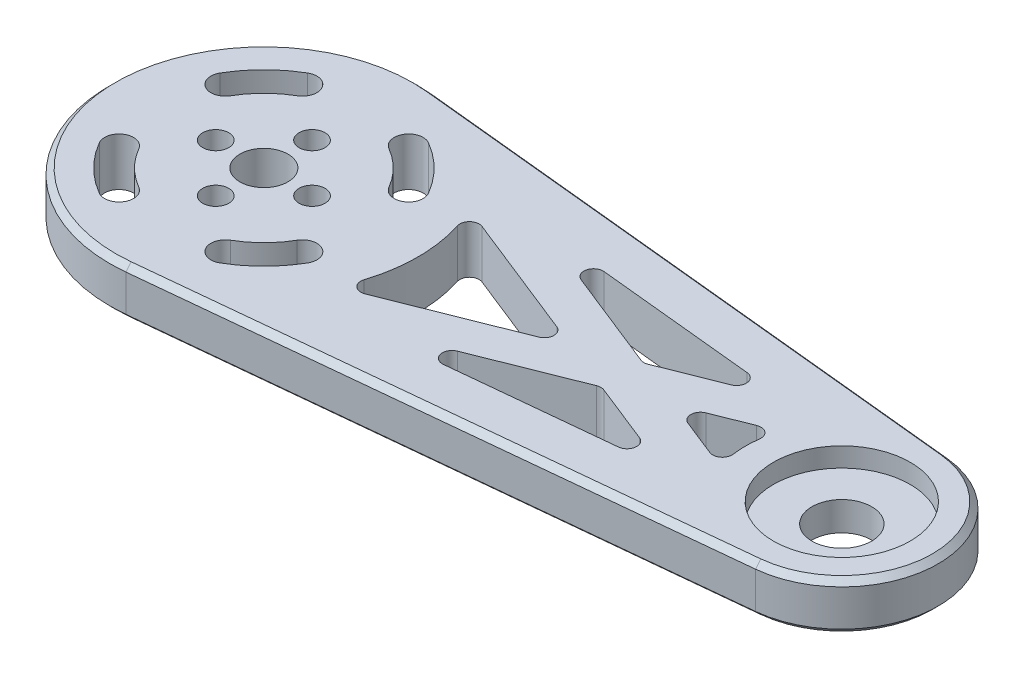
SolidWorks part; units mm, degrees
material "三聚氰胺甲醛树脂"
ref_plane "前视基准面" through (0, 0, 0) normal (0, 0, 1) x (1, 0, 0)
ref_plane "上视基准面" through (0, 0, 0) normal (0, 1, 0) x (1, 0, 0)
ref_plane "右视基准面" through (0, 0, 0) normal (1, 0, 0) x (0, 0, -1)
sketch "草图1" plane through (0, 0, 0) normal (0, 1, 0) x (1, 0, 0)
  line L0 (0, 0) -> (-5.9584, 0) construction
  line L1 (1.6, -15.9198) -> (61, -9.9499)
  line L2 (1.6, 15.9198) -> (61, 9.9499)
  line L3 (19.8889, 9.0565) -> (47.5675, 6.2747)
  line L4 (19.8889, -9.0565) -> (47.5675, -6.2747)
  line L5 (12.6607, 9.783) -> (51.8832, -5.841) construction
  line L6 (12.6607, -9.783) -> (51.8832, 5.841) construction
  line L7 (14.4221, 6.9285) -> (31.8155, 0)
  line L8 (19.8889, 9.0565) -> (37.22, 2.1528)
  line L9 (14.4221, -6.9285) -> (31.8155, 0)
  line L10 (19.8889, -9.0565) -> (37.22, -2.1528)
  line L11 (37.22, 2.1528) -> (47.5675, 6.2747)
  line L12 (42.6245, 0) -> (50.5056, -3.1394)
  line L13 (42.6245, 0) -> (50.5056, 3.1394)
  line L14 (37.22, -2.1528) -> (47.5675, -6.2747)
  line L15 (7.7782, -7.7782) -> (0, 0) construction
  circle A0 centre (0, 0) radius 5 construction
  circle A1 centre (-5, 0) radius 1.35
  circle A2 centre (0, 5) radius 1.35
  circle A3 centre (5, 0) radius 1.35
  circle A4 centre (0, -5) radius 1.35
  arc A5 (1.6, 15.9198) -> (1.6, -15.9198) centre (0, 0) ccw
  circle A6 centre (0, 0) radius 2.5
  arc A7 (50.5056, 3.1394) -> (50.5056, -3.1394) centre (60, 0) ccw
  circle A8 centre (60, 0) radius 3.1
  circle A9 centre (60, 0) radius 7.1
  arc A10 (14.4221, -6.9285) -> (14.4221, 6.9285) centre (0, 0) ccw
  circle A11 centre (0, 0) radius 16 construction
  arc A12 (61, -9.9499) -> (61, 9.9499) centre (60, 0) ccw
  circle A13 centre (60, 0) radius 10 construction
  arc A14 (5.5166, -9.5166) -> (9.5166, -5.5166) centre (0, 0) ccw construction
  arc A15 (6.2689, -10.8144) -> (10.8144, -6.2689) centre (0, 0) ccw
  arc A16 (4.7644, -8.2189) -> (8.2189, -4.7644) centre (0, 0) ccw
  arc A17 (4.7644, -8.2189) -> (6.2689, -10.8144) centre (5.5166, -9.5166) ccw
  arc A18 (10.8144, -6.2689) -> (8.2189, -4.7644) centre (9.5166, -5.5166) ccw
  arc A19 (-9.5166, -5.5166) -> (-5.5166, -9.5166) centre (0, 0) ccw construction
  arc A20 (-10.8144, -6.2689) -> (-6.2689, -10.8144) centre (0, 0) ccw
  arc A21 (-8.2189, -4.7644) -> (-4.7644, -8.2189) centre (0, 0) ccw
  arc A22 (-8.2189, -4.7644) -> (-10.8144, -6.2689) centre (-9.5166, -5.5166) ccw
  arc A23 (-6.2689, -10.8144) -> (-4.7644, -8.2189) centre (-5.5166, -9.5166) ccw
  arc A24 (-5.5166, 9.5166) -> (-9.5166, 5.5166) centre (0, 0) ccw construction
  arc A25 (-6.2689, 10.8144) -> (-10.8144, 6.2689) centre (0, 0) ccw
  arc A26 (-4.7644, 8.2189) -> (-8.2189, 4.7644) centre (0, 0) ccw
  arc A27 (-4.7644, 8.2189) -> (-6.2689, 10.8144) centre (-5.5166, 9.5166) ccw
  arc A28 (-10.8144, 6.2689) -> (-8.2189, 4.7644) centre (-9.5166, 5.5166) ccw
  arc A29 (9.5166, 5.5166) -> (5.5166, 9.5166) centre (0, 0) ccw construction
  arc A30 (10.8144, 6.2689) -> (6.2689, 10.8144) centre (0, 0) ccw
  arc A31 (8.2189, 4.7644) -> (4.7644, 8.2189) centre (0, 0) ccw
  arc A32 (8.2189, 4.7644) -> (10.8144, 6.2689) centre (9.5166, 5.5166) ccw
  arc A33 (6.2689, 10.8144) -> (4.7644, 8.2189) centre (5.5166, 9.5166) ccw
  point P15 (0, 0)
  point P36 (7.7782, -7.7782)
  point P53 (-7.7782, -7.7782)
  point P60 (-7.7782, 7.7782)
  point P67 (7.7782, 7.7782)
  point P72 (0, 0)
  dimension "D1" = 10
  dimension "D2" = 2.7
  dimension "D4" = 20
  dimension "D5" = 32
  dimension "D6" = 5
  dimension "D7" = 6.2
  dimension "D8" = 14.2
  dimension "D15" = 11
  dimension "D16" = 1.5
  dimension "D3" = 60
  dimension "D9" = 5
  dimension "D10" = 5
  dimension "D11" = 2
  dimension "D12" = 2
  dimension "D13" = 2
  dimension "D14" = 2
  dimension "D17" = 4
  dimension "D18" = 45
  dimension "D19" = 4
extrude "凸台-拉伸1" add sketch "草图1" along normal blind 5 contours L1 A7 L2 A5 A9 A1 A2 A3 A4 A6 region at (-15.0824, 0, 0)
extrude "凸台-拉伸2" add sketch "草图1<3>" along normal blind 3 contours A9 A8 region at (53.1008, 0, 0)
sketch "草图1<3>" plane through (0, 0, 0) normal (0, 1, 0) x (1, 0, 0) same geometry as "草图1"
fillet "圆角1" radius 1 12 edges at (42.6245, 2.5, 0) (50.5056, 2.5, -3.1394) (50.5056, 2.5, 3.1394) (47.5675, 2.5, -6.2747) (19.8889, 2.5, -9.0565) (37.22, 2.5, -2.1528) (31.8155, 2.5, 0) (14.4221, 2.5, -6.9285) (14.4221, 2.5, 6.9285) (19.8889, 2.5, 9.0565) (37.22, 2.5, 2.1528) (47.5675, 2.5, 6.2747)
sketch "草图2" plane through (0, 5, 0) normal (0, 1, 0) x (1, 0, 0)
  line L0 (1.35, -13.4323) -> (60.75, -7.4624)
  line L1 (60.75, 7.4624) -> (1.35, 13.4323)
  line L2 (1.6, -15.9198) -> (61, -9.9499)
  line L3 (61, 9.9499) -> (1.6, 15.9198)
  line L4 (1.6, -15.9198) -> (61, -9.9499)
  line L5 (61, 9.9499) -> (1.6, 15.9198)
  arc A0 (1.35, 13.4323) -> (1.35, -13.4323) centre (0, 0) ccw
  arc A1 (60.75, -7.4624) -> (60.75, 7.4624) centre (60, 0) ccw
  arc A2 (61, -9.9499) -> (61, 9.9499) centre (60, 0) ccw
  arc A3 (1.6, 15.9198) -> (1.6, -15.9198) centre (0, 0) ccw
  arc A4 (61, -9.9499) -> (61, 9.9499) centre (60, 0) ccw
  arc A5 (1.6, 15.9198) -> (1.6, -15.9198) centre (0, 0) ccw
  dimension "D1" = 0
  dimension "D2" = 2.5
chamfer "倒角1" distance 0.6 angle 45 8 edges at (31.3, 5, 12.9348) (-16, 5, 0) (70, 5, 0) (31.3, 5, -12.9348) (31.3, 0, 12.9348) (-16, 0, 0) (70, 0, 0) (31.3, 0, -12.9348)
